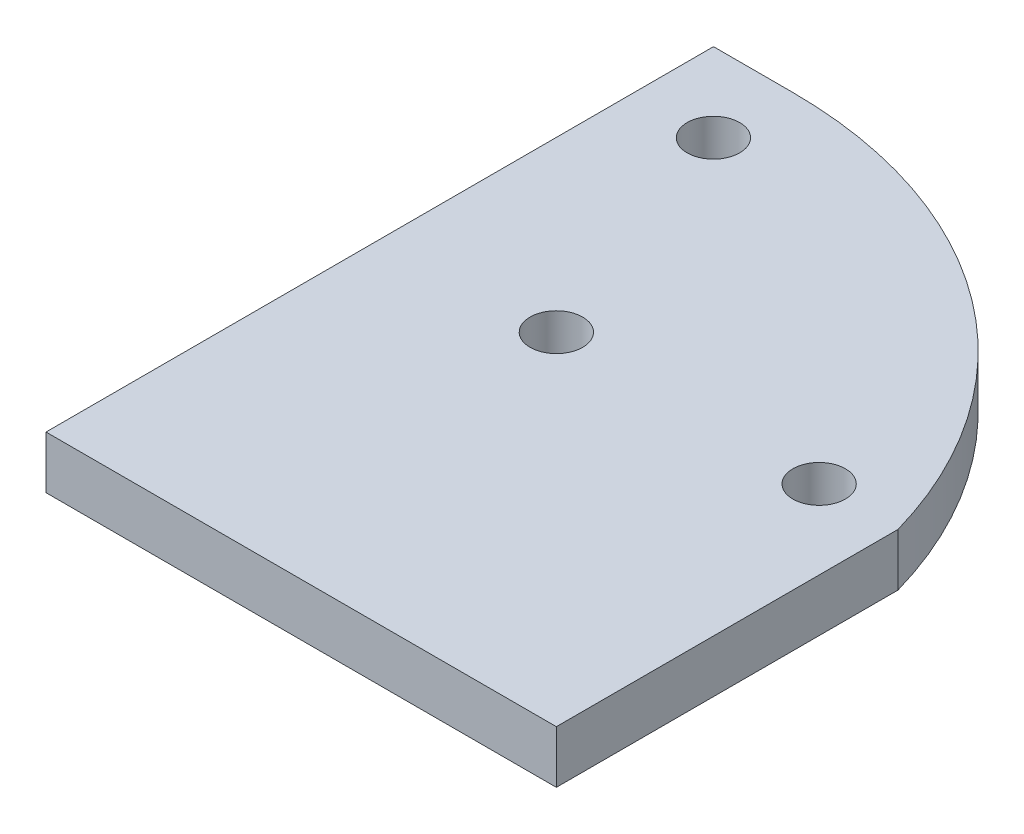
SolidWorks part; units mm, degrees
material "6061 Alloy"
ref_plane "Front Plane" through (0, 0, 0) normal (0, 0, 1) x (1, 0, 0)
ref_plane "Top Plane" through (0, 0, 0) normal (0, 1, 0) x (1, 0, 0)
ref_plane "Right Plane" through (0, 0, 0) normal (1, 0, 0) x (0, 0, -1)
sketch "Sketch1" plane through (0, 0, 0) normal (0, 1, 0) x (1, 0, 0)
  line L0 (0, 0) -> (0, 127)
  line L1 (0, 127) -> (15, 127)
  line L2 (0, 0) -> (97.1, 0)
  line L3 (97.1, 0) -> (97.1, 65)
  line L4 (0, 25) -> (97.1, 25) construction
  arc A0 (15, 127) -> (97.1, 65) centre (15, 41.6419) cw
  dimension "D1" = 97.1
  dimension "D2" = 127
  dimension "D3" = 15
  dimension "D4" = 65
  dimension "D5" = 25
sketch "Sketch2" plane through (0, 0, 0) normal (0, 1, 0) x (1, 0, 0)
  line L0 (14.999, 111.9846) -> (32.1, 65) construction
  line L1 (32.1, 65) -> (82.1, 65) construction
  line L2 (32.1, 65) -> (42.3606, 36.8092) construction
  line L3 (30.6144, 32.534) -> (54.1068, 41.0845) construction
  line L4 (0, 25) -> (97.1, 25) construction
  circle A0 centre (14.999, 111.9846) radius 5
  circle A1 centre (82.1, 65) radius 5
  circle A2 centre (32.1, 65) radius 5
  point P9 (42.3606, 36.8092)
  dimension "D1" = 50
  dimension "D2" = 50
  dimension "D3" = 15
  dimension "D4" = 110
  dimension "D5" = 7.534
extrude "Boss-Extrude1" add sketch "Sketch1" along normal blind 10
extrude "Cut-Extrude4" cut sketch "Sketch2" against normal through all and the other way through all
